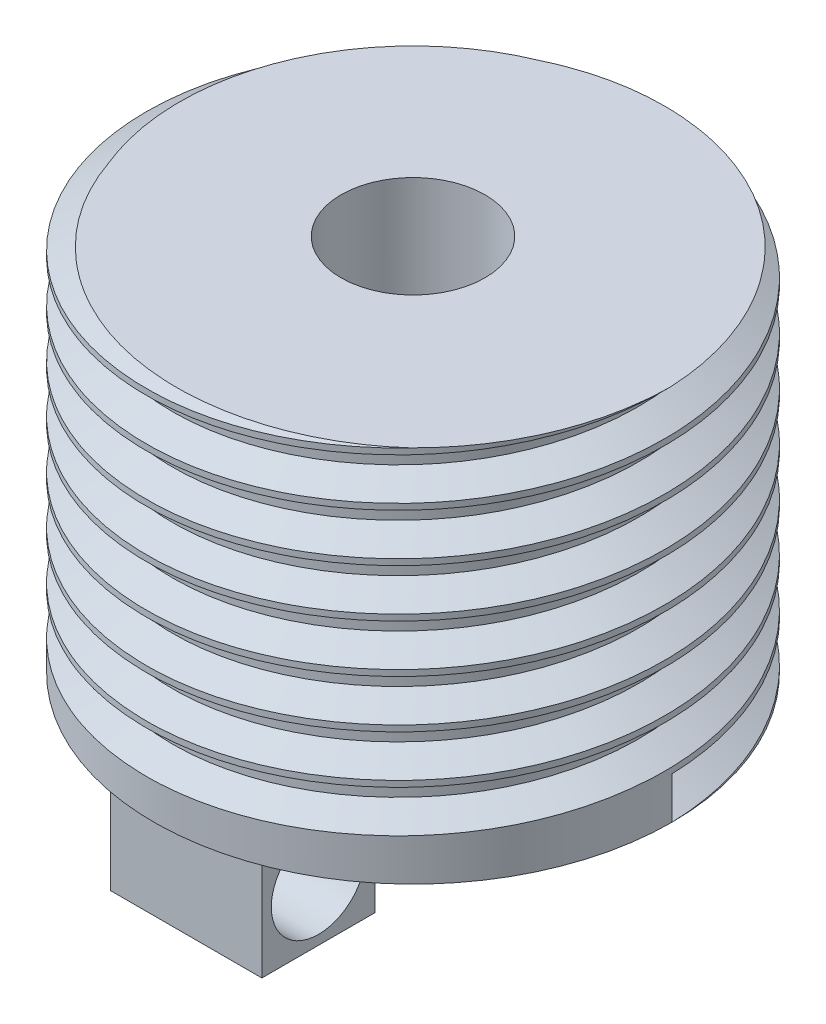
SolidWorks part; units mm, degrees
ref_plane "Front Plane" through (0, 0, 0) normal (0, 0, 1) x (1, 0, 0)
ref_plane "Top Plane" through (0, 0, 0) normal (0, 1, 0) x (1, 0, 0)
ref_plane "Right Plane" through (0, 0, 0) normal (1, 0, 0) x (0, 0, -1)
sketch "Sketch1" plane through (0, 0, 0) normal (0, 1, 0) x (1, 0, 0)
  circle A0 centre (0, 0) radius 6.858
  dimension "D1" = 13.716
extrude "Boss-Extrude1" add sketch "Sketch1" along normal blind 10 contours A0
thread "Thread1" pitch 1.27 method cut profile "Thread Profile4" start angle 0, offset 0, length 10, pitch 1.27, diameter 13.716
ref_plane "Plane4" through (6.858, 0, 0) normal (0, 0, 1) x (1, 0, 0)
sketch "Thread Profile4" plane through (6.858, 0, 0) normal (0, 0, 1) x (1, 0, 0)
  line L0 (0, 0) -> (0, 1.27) construction
  line L11 (0, 0) -> (0, 1.1112)
  line L12 (0, 1.1112) -> (-0.6874, 0.7144)
  line L13 (-0.6874, 0.7144) -> (-0.6874, 0.3969)
  line L15 (-0.6874, 0.3969) -> (0, 0)
  line L17 (-0.6874, 0.5556) -> (0, 0.5556) construction
  point P2 (0, 0)
  dimension "Pitch" = 1.27
  dimension "Profile_Angle" = 60
  dimension "Profile_Land" = 0.3175
  dimension "Profile_Height" = 0.6874
sketch "Sketch15" plane through (0, 0, 0) normal (0, -1, 0) x (1, 0, 0)
  circle A0 centre (0, 0) radius 1.905
  dimension "D1" = 3.81
extrude "Cut-Extrude1" cut sketch "Sketch15" against normal up to surface (10 mm away) up to face at (1.6775, 9.9999, 0.7215)
sketch "Sketch16" plane through (0, 0, 0) normal (1, 0, 0) x (0, 0, -1)
  line L1 (-6, -3) -> (-3, -3)
  line L2 (-6, -3) -> (-6, 0)
  line L3 (-6, 0) -> (-3, 0)
  line L4 (-3, -3) -> (-3, 0)
  line L5 (0, 5.7327) -> (0, -5.7327) construction
  line L7 (3, -3) -> (3, 0)
  line L8 (6, -3) -> (3, -3)
  line L9 (6, -3) -> (6, 0)
  line L10 (-6.858, 0) -> (6.858, 0) construction
  line L11 (6, 0) -> (3, 0)
  line L12 (3, -3) -> (3, 0)
  line L13 (6, -3) -> (3, -3)
  line L14 (6, -3) -> (6, 0)
  point P12 (0, 0)
  point P13 (0, 0)
  dimension "D1" = 3
  dimension "D2" = 3
  dimension "D3" = 6
extrude "Boss-Extrude2" add sketch "Sketch16" along normal blind 2 and the other way blind 2 contours L9 L11 L7 L8 | L2 L1 L4 L3 region at (0, -1.5, -4.5)
sketch "Sketch17" plane through (-2, 0, 0) normal (-1, 0, 0) x (0, 0, 1)
  line L1 (3, -3) -> (3, 0) construction
  line L8 (0, -5.7327) -> (0, 5.7327) construction
  circle A0 centre (4.5, -1.5) radius 1.25
  circle A1 centre (-4.5, -1.5) radius 1.25
  point P2 (0, 0)
  point P6 (-3.0067, -1.5)
  point P7 (2.3107, -1.5)
  point P9 (0, 0)
  point P14 (-2.3107, -1.5)
  dimension "D1" = 2.5
  dimension "D2" = 1.5
extrude "Cut-Extrude2" cut sketch "Sketch17" against normal up to surface (4 mm away) up to face at (2, -1.5, 4.5)
